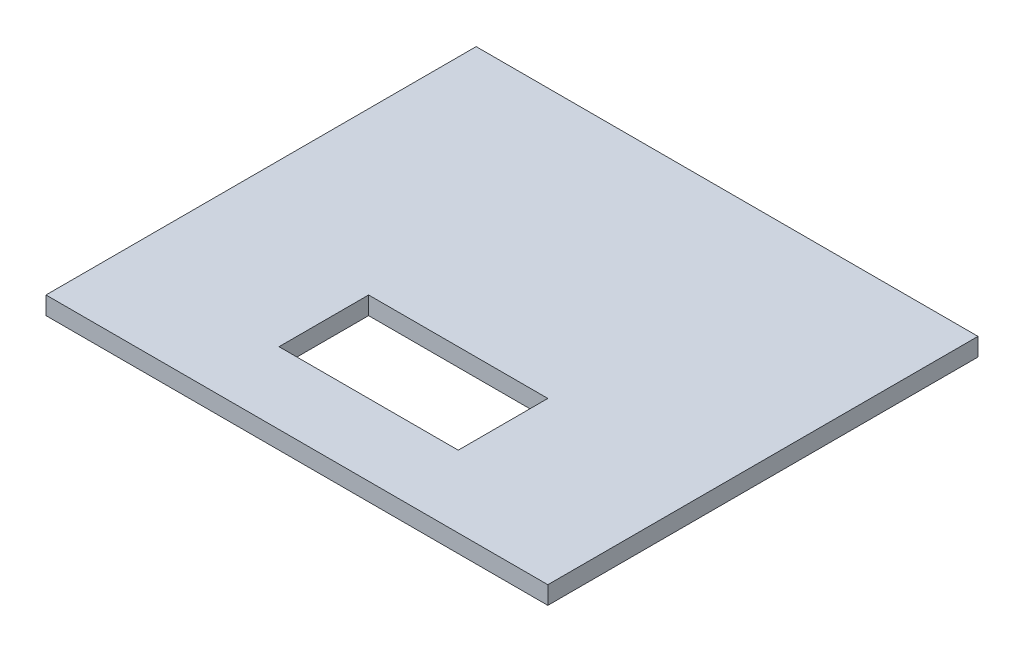
SolidWorks part; units mm, degrees
material "Oak"
ref_plane "Front Plane" through (0, 0, 0) normal (0, 0, 1) x (1, 0, 0)
ref_plane "Top Plane" through (0, 0, 0) normal (0, 1, 0) x (1, 0, 0)
ref_plane "Right Plane" through (0, 0, 0) normal (1, 0, 0) x (0, 0, -1)
sketch "Sketch1" plane through (0, 0, 0) normal (0, 1, 0) x (1, 0, 0)
  line L1 (-88.9, -76.2) -> (88.9, -76.2)
  line L2 (-88.9, -76.2) -> (-88.9, 76.2)
  line L3 (-88.9, 76.2) -> (88.9, 76.2)
  line L4 (88.9, -76.2) -> (88.9, 76.2)
  line L5 (-88.9, -76.2) -> (88.9, 76.2) construction
  line L6 (-88.9, 76.2) -> (88.9, -76.2) construction
  point P0 (0, 0)
  dimension "D1" = 152.4
  dimension "D2" = 177.8
extrude "Boss-Extrude1" add sketch "Sketch1" along normal blind 6.35
sketch "Sketch2" plane through (0, 6.35, 0) normal (0, 1, 0) x (1, 0, 0)
  line L0 (0, -76.2) -> (0, -34.925) construction
  line L1 (-88.9, -76.2) -> (88.9, -76.2) construction
  line L3 (-31.75, -19.05) -> (31.75, -19.05)
  line L4 (-31.75, -19.05) -> (-31.75, -50.8)
  line L5 (-31.75, -50.8) -> (31.75, -50.8)
  line L6 (31.75, -19.05) -> (31.75, -50.8)
  line L7 (-31.75, -19.05) -> (31.75, -50.8) construction
  line L8 (-31.75, -50.8) -> (31.75, -19.05) construction
  line L9 (88.9, 76.2) -> (-88.9, 76.2) construction
  dimension "D1" = 63.5
  dimension "D2" = 31.75
  dimension "D3" = 111.125
extrude "Cut-Extrude1" cut sketch "Sketch2" against normal through all
